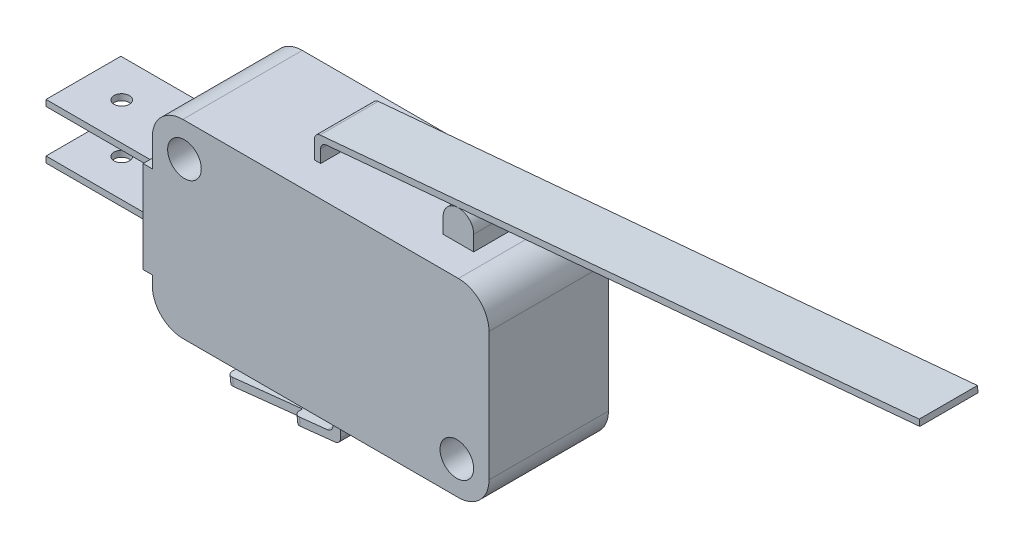
SolidWorks part; units mm, degrees
note: '?' marks a value the reader was unsure of. The reader was unsure of these and kept them because the rebuilt part matched: shared geometry of "Sketch", "Sketch".
ref_plane "Front Plane" through (0, 0, 0) normal (0, 0, 1) x (1, 0, 0)
ref_plane "Top Plane" through (0, 0, 0) normal (0, 1, 0) x (1, 0, 0)
ref_plane "Right Plane" through (0, 0, 0) normal (1, 0, 0) x (0, 0, -1)
sketch "Sketch1" plane through (0, 0, 0) normal (0, 0, 1) x (1, 0, 0)
  line L0 (0, 7.874) -> (0, -7.874) construction
  line L1 (-13.97, 0) -> (13.97, 0) construction
  line L2 (11.43, 7.874) -> (-11.43, 7.874)
  line L3 (-13.97, 5.334) -> (-13.97, 3.048)
  line L4 (-13.97, 3.048) -> (-14.732, 3.048)
  line L5 (-14.732, 3.048) -> (-14.732, -4.572)
  line L6 (-14.732, -4.572) -> (-13.97, -4.572)
  line L7 (-13.97, -4.572) -> (-13.97, -5.334)
  line L8 (-11.43, -7.874) -> (11.43, -7.874)
  line L9 (13.97, -5.334) -> (13.97, 5.334)
  arc A0 (-11.43, 7.874) -> (-13.97, 5.334) centre (-11.43, 5.334) ccw
  arc A1 (-13.97, -5.334) -> (-11.43, -7.874) centre (-11.43, -5.334) ccw
  arc A2 (11.43, -7.874) -> (13.97, -5.334) centre (11.43, -5.334) ccw
  arc A3 (13.97, 5.334) -> (11.43, 7.874) centre (11.43, 5.334) ccw
  circle A4 centre (-11.3, 5.08) radius 1.395
  circle A5 centre (11.3, -5.16) radius 1.395
  dimension "D3" = 2.54
  dimension "D8" = 2.79
  dimension "D1" = 28.702
  dimension "D2" = 15.748
  dimension "D4" = 7.874
  dimension "D5" = 7.62
  dimension "D6" = 4.826
  dimension "D7" = 0.762
  dimension "D9" = 11.3
  dimension "D10" = 5.08
  dimension "D11" = 11.3
  dimension "D12" = 5.16
extrude "Extrude1" add sketch "Sketch1" along normal mid plane 9.91 contours A4 | L9 A3 L2 A0 L3 L4 L5 L6 L7 A1 L8 A2 A5 A4 | A5
sketch "Sketch2" plane through (0, 0, 0) normal (0, 0, 1) x (1, 0, 0)
  line L0 (-24.638, -2.794) -> (-14.732, -2.794)
  line L1 (-14.732, -2.286) -> (-24.638, -2.286)
  line L2 (-24.638, -2.286) -> (-24.638, -2.794)
  line L3 (-24.638, 1.27) -> (-14.732, 1.27)
  line L4 (-14.732, 1.778) -> (-24.638, 1.778)
  line L5 (-24.638, 1.778) -> (-24.638, 1.27)
  line L6 (0, 0) -> (-27.6869, 0) construction
  line L8 (-14.732, 1.778) -> (-14.732, 1.27)
  line L9 (-14.732, -2.286) -> (-14.732, -2.794)
  line L10 (-14.732, 3.048) -> (-14.732, -4.572) construction
  dimension "D1" = 3.556
  dimension "D2" = 1.27
  dimension "D3" = 0.508
  dimension "D4" = 0.508
  dimension "D5" = 9.906
  dimension "D6" = 9.906
extrude "Extrude2" add sketch "Sketch2" along normal mid plane 6.21
sketch "Sketch3" plane through (0, 0, 0) normal (0, 0, 1) x (1, 0, 0)
  line L0 (0, 0) -> (0, 7.874) construction
  line L2 (10.16, 7.874) -> (10.16, 9.139)
  line L3 (7.62, 9.139) -> (7.62, 7.874)
  line L4 (7.62, 7.874) -> (10.16, 7.874)
  line L5 (-3.048, 7.874) -> (-2.54, 7.874)
  line L6 (-2.54, 7.874) -> (-2.54, 9.398)
  line L7 (-2.54, 9.398) -> (47.1735, 13.839)
  line L8 (47.1735, 13.839) -> (47.1283, 14.345)
  line L9 (47.1283, 14.345) -> (-3.048, 9.8626)
  line L10 (-3.048, 9.8626) -> (-3.048, 7.874)
  line L11 (11.43, 7.874) -> (-11.43, 7.874) construction
  arc A0 (10.16, 9.139) -> (7.62, 9.139) centre (8.89, 9.139) ccw
  dimension "D5" = 1.265
  dimension "D6" = 47.1735
  dimension "D7" = 47.1283
  dimension "D1" = 2.54
  dimension "D2" = 10.16
  dimension "D3" = 0.508
  dimension "D4" = 2.54
  dimension "D8" = 1.524
  dimension "D9" = 95.105
extrude "Extrude3" add sketch "Sketch3" along normal mid plane 4.83 contours L9 L10 L5 L6 L7 L8 | L2 A0 L3 L4
sketch "Sketch4" plane through (0, 0, 0) normal (0, 0, 1) x (1, 0, 0)
  line L0 (-11.43, -7.874) -> (11.43, -7.874) construction
  line L6 (-0.38, -10.984) -> (-0.38, -7.874)
  line L7 (-0.38, -7.874) -> (-1.015, -7.874)
  line L8 (-1.015, -7.874) -> (-1.015, -10.414)
  line L9 (-1.015, -10.414) -> (-10.6125, -11.4524)
  line L11 (-10.5441, -12.0837) -> (-0.38, -10.984)
  line L18 (-10.6125, -11.4524) -> (-10.5441, -12.0837)
  dimension "D4" = 2.54
  dimension "D1" = 0.635
  dimension "D2" = 0.635
  dimension "D3" = 9.5975
  dimension "D5" = 3.11
  dimension "D6" = 0.38
extrude "Extrude4" add sketch "Sketch4" along normal mid plane 5.84
sketch "Sketch5" plane through (1.1703, -10.8163, 0) normal (0.1076, -0.9942, 0) x (0.9942, 0.1076, 0)
  line L0 (0, 0) -> (-11.7828, 0) construction
  line L1 (-1.6376, 2.92) -> (-5.4316, 2.92)
  line L2 (-5.4316, 2.92) -> (-5.4316, 2.158)
  line L3 (-5.4316, 2.158) -> (-11.7828, 2.158)
  line L4 (-11.7828, 2.158) -> (-11.7828, -2.16)
  line L5 (-11.7828, -2.16) -> (-5.4316, -2.16)
  line L6 (-5.4316, -2.16) -> (-5.4316, -2.92)
  line L7 (-5.4316, -2.92) -> (-1.6376, -2.92)
  line L8 (-1.6376, -2.92) -> (-1.6376, 2.92)
  line L9 (-11.7828, 2.92) -> (-11.7828, -2.92) construction
  line L12 (-11.7828, -2.92) -> (-1.5594, -2.92) construction
  line L14 (-11.7828, 2.92) -> (-1.5594, 2.92) construction
  circle A0 centre (-8.1018, 0) radius 0.762
  line M1 (-11.7828, -2.92) -> (-1.5594, -2.92)
  line M3 (-1.5594, 2.92) -> (-11.7828, 2.92)
  line M4 (-11.7828, 2.92) -> (-11.7828, -2.92)
  dimension "D1" = 1.524
  dimension "D3" = 4.318
  dimension "D4" = 6.3512
  dimension "D2" = 8.1018
  dimension "D5" = 2.16
  dimension "D6" = 1.6376
extrude "Extrude5" cut sketch "Sketch5" against normal up to next contours L3 L2 M3 M4 | L6 L5 M4 M1
extrude "Extrude6" cut sketch "Sketch" against normal up to next contours A0 L0 | L0 A0
sketch "Sketch" plane through (1.1703, -10.8163, 0) normal (0.1076, -0.9942, 0) x (0.9942, 0.1076, 0) same geometry as "Sketch5"
fillet "Fillet1" radius 0.508 8 edges at (-2.54, 9.398, 0) (-3.048, 9.8626, 0) (-1.015, -10.414, 0) (-0.38, -10.984, 0) (-10.5783, -11.7681, -2.16) (-10.5783, -11.7681, 2.158) (-4.264, -11.0849, 2.92) (-4.264, -11.0849, -2.92)
sketch "Sketch6" plane through (0, -2.794, 0) normal (0, -1, 0) x (1, 0, 0)
  line L0 (0, 0) -> (-14.732, 0) construction
  line L1 (-14.732, 3.105) -> (-14.732, -3.105) construction
  circle A0 centre (-21.462, 0) radius 0.635
  dimension "D1" = 1.27
  dimension "D2" = 6.73
extrude "Extrude7" cut sketch "Sketch6" against normal up to surface (4.572 mm away) up to face at (-19.685, 1.778, 0)
extrude "Extrude8" cut sketch "Sketch" against normal mid plane 15.84 contours A4 | A5
sketch "Sketch" plane through (0, 0, 0) normal (0, 0, 1) x (1, 0, 0) same geometry as "Sketch1"
sketch "Sketch8" plane through (1.102, -10.1849, 0) normal (-0.1076, 0.9942, 0) x (0.9942, 0.1076, 0)
  point P0 (-8.1018, 0)
ref_plane "Plane1" through (-8.0548, -0.8715, 0) normal (-0.9942, -0.1076, 0) x (0, 0, 1)
sketch "Sketch10" plane through (0, -2.794, 0) normal (0, -1, 0) x (-1, 0, 0)
  point P0 (21.462, 0)
ref_plane "Plane2" through (-21.462, 0, 0) normal (-1, 0, 0) x (0, 0, 1)
sketch "0_0_Point" plane through (-8.0548, -0.8715, 0) normal (-0.9942, -0.1076, 0) x (0, 0, 1)
  point P0 (0, -10.5619)
other "0_0" parameters "Diameter"=2, "StubLength"=2
ref_axis "Axis1" through (-16.8606, -12.4478, 0) along (0.9942, 0.1076, 0)?
sketch "1_0_Point" plane through (-21.462, 0, 0) normal (-1, 0, 0) x (0, 0, 1)
  point P0 (0, -2.54)
other "1_0" parameters "Diameter"=2, "StubLength"=2
ref_axis "Axis2" through (-31.462, -2.54, 0) along (1, 0, 0)?
sketch "2_0_Point" plane through (-21.462, 0, 0) normal (-1, 0, 0) x (0, 0, 1)
  point P0 (0, 1.524)
other "2_0" parameters "Diameter"=2, "StubLength"=2
ref_axis "Axis3" through (-31.462, 1.524, 0) along (1, 0, 0)?
